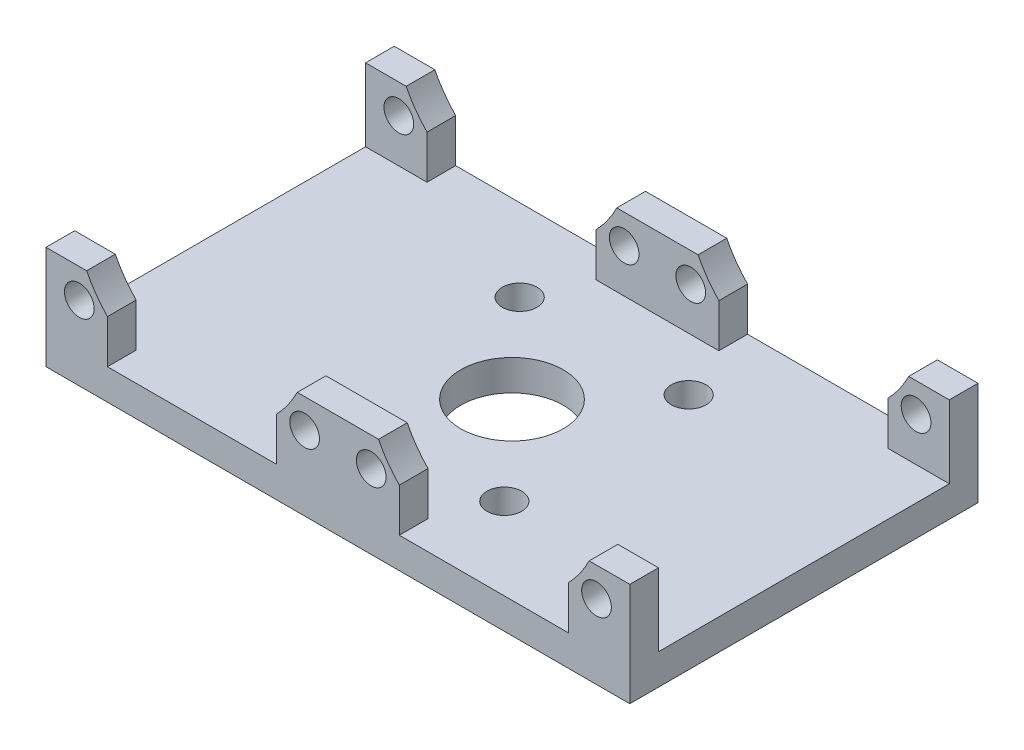
SolidWorks part; units mm, degrees
ref_plane "Front Plane" through (0, 0, 0) normal (0, 0, 1) x (1, 0, 0)
ref_plane "Top Plane" through (0, 0, 0) normal (0, 1, 0) x (1, 0, 0)
ref_plane "Right Plane" through (0, 0, 0) normal (1, 0, 0) x (0, 0, -1)
sketch "Sketch1" plane through (0, 0, 0) normal (0, 1, 0) x (1, 0, 0)
  line L1 (-28.5, 17) -> (28.5, 17)
  line L2 (-28.5, 17) -> (-28.5, -17)
  line L3 (-28.5, -17) -> (28.5, -17)
  line L4 (28.5, 17) -> (28.5, -17)
  line L5 (-28.5, 17) -> (28.5, -17) construction
  line L6 (-28.5, -17) -> (28.5, 17) construction
  circle A0 centre (0, 0) radius 5
  circle A1 centre (-8.25, 9) radius 1.7
  circle A5 centre (8.25, 9) radius 1.7
  circle A6 centre (8.25, -9) radius 1.7
  circle A7 centre (-8.25, -9) radius 1.7
  point P0 (0, 0)
  dimension "D3" = 10
  dimension "D4" = 3.4
  dimension "D5" = 8.25
  dimension "D8" = 2
  dimension "D6" = 9
  dimension "D1" = 57
  dimension "D2" = 34
  dimension "D7" = 2
extrude "Boss-Extrude1" add sketch "Sketch1" along normal blind 3
ref_plane "Plane2" through (0, 0, 0) normal (0, 0, 1) x (1, 0, 0)
sketch "Sketch6" plane through (0, 0, 17) normal (0, 0, 1) x (1, 0, 0)
  line L0 (-22.5, 3) -> (-6, 3) construction
  line L1 (-28.5, 3) -> (-22.5, 3)
  line L2 (-28.5, 3) -> (-28.5, 10.1)
  line L3 (-28.5, 10.1) -> (-22.5, 10.1)
  line L4 (-22.5, 3) -> (-22.5, 10.1)
  line L5 (-28.5, 3) -> (28.5, 3) construction
  line L6 (22.5, 3) -> (6, 3) construction
  line L7 (-6, 3) -> (0, 3)
  line L8 (-6, 3) -> (-6, 10.1)
  line L9 (-6, 10.1) -> (0, 10.1)
  line L10 (0, 3) -> (0, 10.1)
  line L11 (0, 3) -> (6, 3)
  line L12 (0, 3) -> (0, 10.1)
  line L13 (0, 10.1) -> (6, 10.1)
  line L14 (6, 3) -> (6, 10.1)
  line L15 (28.5, 3) -> (22.5, 3)
  line L16 (28.5, 3) -> (28.5, 10.1)
  line L17 (28.5, 10.1) -> (22.5, 10.1)
  line L18 (22.5, 3) -> (22.5, 10.1)
  line L19 (14.25, 3) -> (14.25, 12.5555) construction
  line L20 (-6, 3) -> (-22.5, 3) construction
  line L21 (-14.25, 3) -> (-14.25, 11.3572) construction
  circle A1 centre (-3.25, 7.25) radius 1.45
  circle A2 centre (3.25, 7.25) radius 1.45
  circle A3 centre (25.25, 7.25) radius 1.45
  circle A4 centre (-25.25, 7.25) radius 1.45
  circle A5 centre (14.25, 15.25) radius 11.5
  circle A6 centre (-14.25, 15.25) radius 11.5
  point P34 (0, 0)
  line M16 (28.5, 3) -> (-28.5, 3)
  dimension "D9" = 2.9
  dimension "D10" = 3.25
  dimension "D11" = 2.85
  dimension "D12" = 2.85
  dimension "D13" = 3.25
  dimension "D14" = 12.25
  dimension "D15" = 12.25
  dimension "D1" = 6
  dimension "D2" = 7.1
  dimension "D3" = 16.5
  dimension "D4" = 6
  dimension "D5" = 7.1
  dimension "D6" = 6
  dimension "D7" = 6
  dimension "D8" = 7.1
extrude "Boss-Extrude3" add sketch "Sketch6" against normal blind 2.8 contours A5 L18 L16 L17 A3 M16 | A5 L13 L10 L14 A2 M16 | A6 L8 L10 L9 A1 M16 | A6 L3 L2 L4 A4 M16 region at (-28.407, 6.55, 17) region at (-5.907, 5.1191, 17) region at (0.093, 6.55, 17) region at (22.593, 5.1191, 17)
mirror "Mirror2" about plane through (0, 0, 0) normal (0, 0, 1) of "Boss-Extrude3"
